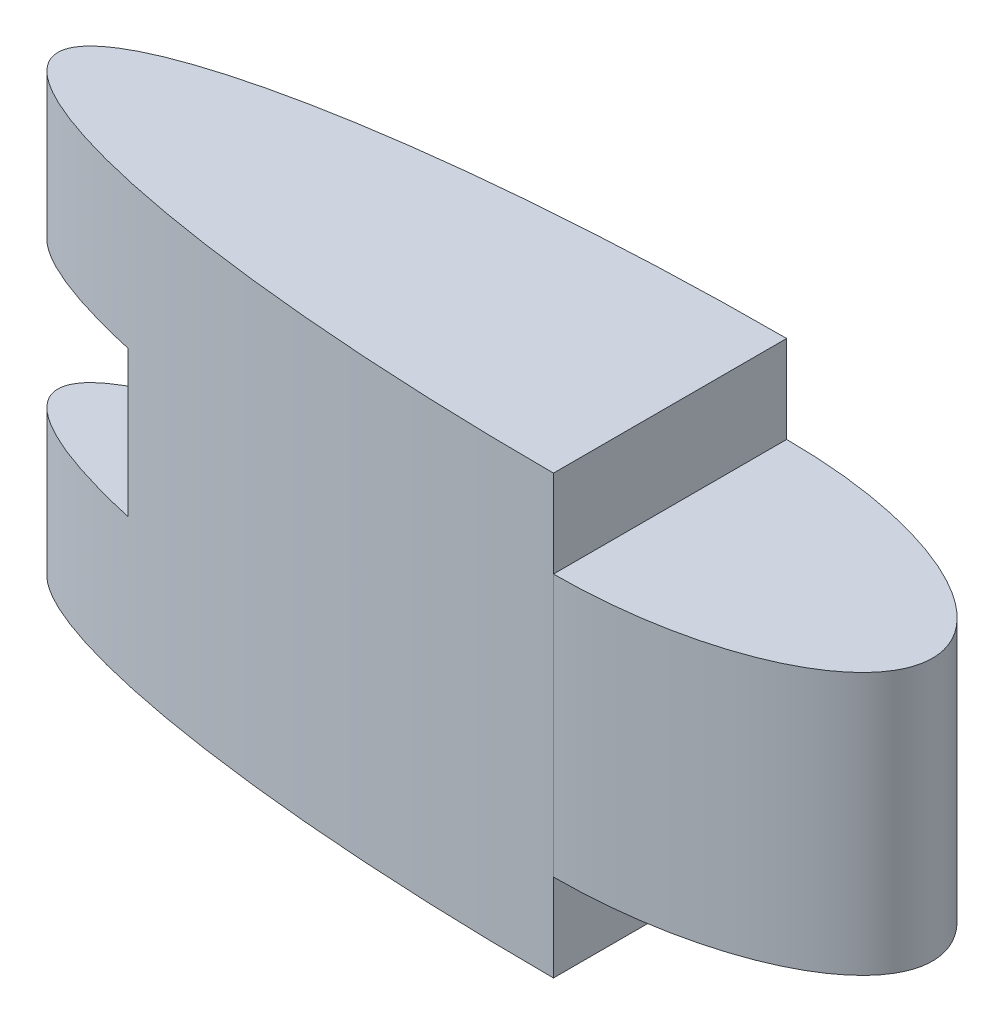
SolidWorks part; units mm, degrees
ref_plane "Alzado" through (0, 0, 0) normal (0, 0, 1) x (1, 0, 0)
ref_plane "Planta" through (0, 0, 0) normal (0, 1, 0) x (1, 0, 0)
ref_plane "Vista lateral" through (0, 0, 0) normal (1, 0, 0) x (0, 0, -1)
sketch "Sketch1" plane through (0, 0, 0) normal (0, 1, 0) x (1, 0, 0)
  line L3 (-210, 0) -> (210, 0) construction
  line L4 (-90, 0) -> (90, 0) construction
  ellipse E2 centre (0, 0) end of major axis (-90, 0) minor radius 40 (0, -40) -> (0, 40) ccw
  ellipse E3 centre (0, 0) end of major axis (210, 0) minor radius 40 (0, 40) -> (0, -40) ccw
  point P1 (0, 0)
  point P2 (0, 0)
  dimension "D5" = 80
  dimension "D6" = 210
  dimension "D7" = 90
extrude "Boss-Extrude1" add sketch "Sketch1" along normal blind 150
sketch "Sketch2" plane through (0, 0, 0) normal (0, 0, 1) x (1, 0, 0)
  line L0 (0, 0) -> (90, 0) construction
  point P4 (45, 0)
ref_axis "Axis1" through (45, 0, 0) along (0, -1, 0)
sketch "Sketch3" plane through (0, 0, 0) normal (0, 0, 1) x (1, 0, 0)
  line L0 (-210, 150) -> (-210, 0) construction
  line L1 (90, 150) -> (0, 150)
  line L2 (90, 150) -> (90, 120)
  line L3 (90, 120) -> (0, 120)
  line L4 (0, 150) -> (0, 120)
  line L5 (90, 0) -> (0, 0)
  line L6 (90, 0) -> (90, 30)
  line L7 (90, 30) -> (0, 30)
  line L8 (0, 0) -> (0, 30)
  line L9 (-210, 100) -> (-160, 100)
  line L10 (-210, 100) -> (-210, 50)
  line L11 (-210, 50) -> (-160, 50)
  line L12 (-160, 100) -> (-160, 50)
  line L13 (0, 150) -> (-210, 150) construction
  dimension "D1" = 90
  dimension "D2" = 30
  dimension "D3" = 30
  dimension "D4" = 90
  dimension "D5" = 50
  dimension "D6" = 50
  dimension "D7" = 50
extrude "Cut-Extrude1" cut sketch "Sketch3" against normal up to next and the other way up to next
sketch "Sketch4" plane through (0, 100, 0) normal (0, -1, 0) x (1, 0, 0)
  line L0 (0, 0) -> (-312.1296, 0) construction
  ellipse E0 centre (0, 0) end of major axis (210, 0) minor radius 40 (0, 40) -> (0, -40) ccw construction
  point P1 (-210, 0)
  point P2 (-185, 0)
  point P12 (0, 0)
  point P13 (0, 0)
  point P14 (0, 0)
  dimension "D1" = 25
ref_axis "Axis2" through (-185, 100, 0) along (0, -1, 0)
